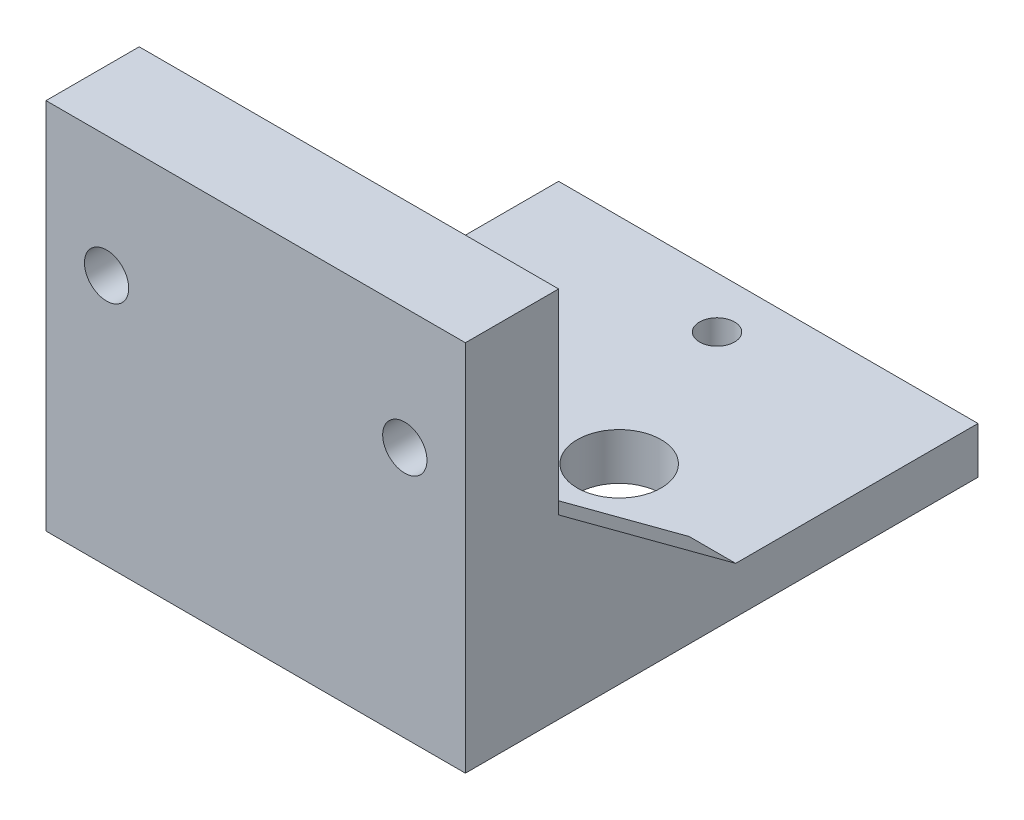
SolidWorks part; units mm, degrees
ref_plane "Front Plane" through (0, 0, 0) normal (0, 0, 1) x (1, 0, 0)
ref_plane "Top Plane" through (0, 0, 0) normal (0, 1, 0) x (1, 0, 0)
ref_plane "Right Plane" through (0, 0, 0) normal (1, 0, 0) x (0, 0, -1)
sketch "Sketch7" plane through (0, 0, 0) normal (0, 1, 0) x (1, 0, 0)
  line L0 (28.2563, -140.551) -> (-16.7437, -140.551)
  line L1 (28.2563, -95.551) -> (-16.7437, -95.551)
  line L2 (28.2563, -95.551) -> (28.2563, -142.551)
  line L3 (28.2563, -142.551) -> (-16.7437, -142.551)
  line L4 (-16.7437, -95.551) -> (-16.7437, -142.551)
  line L5 (28.2563, -95.551) -> (-16.7437, -142.551) construction
  line L6 (28.2563, -142.551) -> (-16.7437, -95.551) construction
  line L8 (28.2563, -142.551) -> (-16.7437, -142.551)
  line L9 (28.2563, -142.551) -> (28.2563, -150.551)
  line L10 (28.2563, -150.551) -> (-16.7437, -150.551)
  line L11 (-16.7437, -142.551) -> (-16.7437, -150.551)
  circle A0 centre (12.7563, -118.551) radius 4.5
  circle A1 centre (5.362, -118.9853) radius 14
  circle A2 centre (5.7563, -101.051) radius 1.875
  circle A3 centre (5.7563, -136.051) radius 1.875
  circle A4 centre (12.7563, -118.551) radius 3
  point P0 (5.7563, -119.051)
  dimension "D9" = 3.75
  dimension "D10" = 3.75
  dimension "D1" = 47
  dimension "D2" = 45
  dimension "D3" = 2
  dimension "D4" = 7
  dimension "D5" = 7
  dimension "D6" = 17.5
  dimension "D7" = 17.5
  dimension "D8" = 24
  dimension "D11" = 8
extrude "Boss-Extrude5" add sketch "Sketch7" along normal blind 5 separate body contours L1 L4 L0 L2 A3 A2 A1 | A1 A0 region at (5.7563, 0, 139.9146) region at (4.5101, 0, 119.0354)
extrude "Boss-Extrude6" add sketch "Sketch7<3>" along normal blind 40 contours L0 L4 L3 L2 region at (5.7563, 0, 141.551)
sketch "Sketch7<3>" plane through (0, 0, 0) normal (0, 1, 0) x (1, 0, 0) same geometry as "Sketch7"
sketch "Sketch8" plane through (-16.7437, 0, 0) normal (-1, 0, 0) x (0, 0, 1)
  line L0 (140.551, 11) -> (140.551, 5)
  line L1 (140.551, 40) -> (140.551, 5) construction
  line L2 (95.551, 5) -> (140.551, 5) construction
  line L3 (121.551, 5) -> (140.551, 19)
  line L4 (140.551, 19) -> (140.551, 11)
  line L5 (140.551, 5) -> (121.551, 5)
  dimension "D1" = 0
  dimension "D2" = 6
  dimension "D3" = 19
  dimension "D4" = 14
extrude "Boss-Extrude7" add sketch "Sketch8" against normal blind 5
ref_plane "Plane2" through (5.7563, 0, 0) normal (-1, 0, 0) x (0, 0, 1)
mirror "Mirror2" about plane through (5.7563, 0, 0) normal (-1, 0, 0) of "Boss-Extrude7"
sketch "Sketch9" plane through (0, 0, 142.551) normal (0, 0, 1) x (1, 0, 0)
  line L0 (5.7563, 22) -> (5.7563, -22) construction
  line L1 (-15.2437, 34) -> (26.7563, 34)
  line L2 (-15.2437, 34) -> (-15.2437, 20)
  line L3 (-15.2437, 20) -> (26.7563, 20)
  line L4 (26.7563, 34) -> (26.7563, 20)
  line L5 (-15.2437, 34) -> (26.7563, 20) construction
  line L6 (-15.2437, 20) -> (26.7563, 34) construction
  line L7 (28.2563, 0) -> (-16.7437, 0) construction
  point P0 (5.7563, 27)
  dimension "D1" = 20
  dimension "D2" = 14
  dimension "D3" = 42
extrude "Boss-Extrude8" add sketch "Sketch7<4>" along normal up to surface (40 mm away) contours L3 L11 L10 L9 region at (5.7563, 0, 146.551) up to face at (5.7563, 40, 141.551)
sketch "Sketch7<4>" plane through (0, 0, 0) normal (0, 1, 0) x (1, 0, 0) same geometry as "Sketch7"
sketch "Sketch10" plane through (0, 0, 142.551) normal (0, 0, 1) x (1, 0, 0)
  line L0 (26.7563, 34) -> (26.7563, 20) construction
  line L1 (-15.2437, 34) -> (26.7563, 34) construction
  line L2 (-15.2437, 34) -> (-15.2437, 20) construction
  circle A0 centre (21.7563, 27) radius 2.375
  circle A1 centre (-10.2437, 27) radius 2.375
  dimension "D1" = 5
  dimension "D2" = 4.75
  dimension "D4" = 4.75
  dimension "D3" = 7
  dimension "D5" = 7
  dimension "D6" = 5
extrude "Cut-Extrude2" cut sketch "Sketch10" against normal blind 5 and the other way through all
